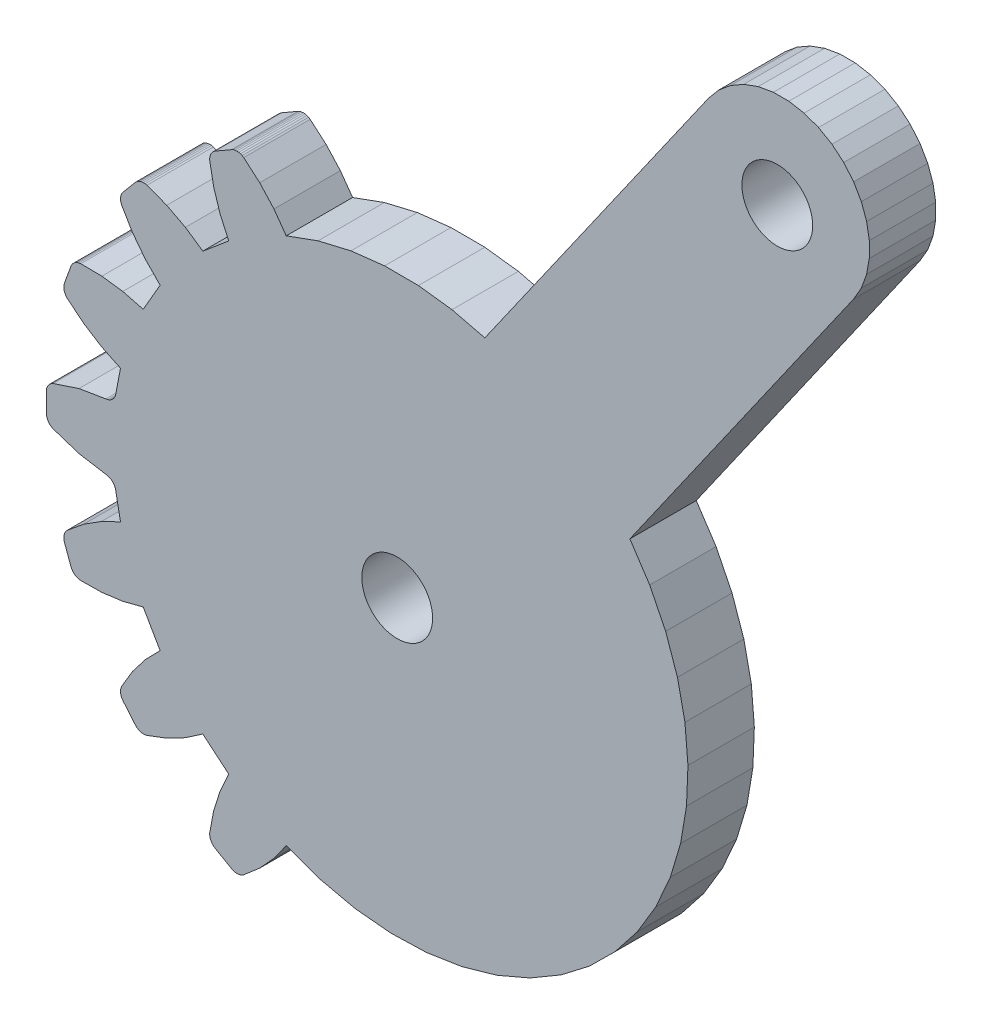
SolidWorks part; units mm, degrees
ref_plane "Front Plane" through (0, 0, 0) normal (0, 0, 1) x (1, 0, 0)
ref_plane "Top Plane" through (0, 0, 0) normal (0, 1, 0) x (1, 0, 0)
ref_plane "Right Plane" through (0, 0, 0) normal (1, 0, 0) x (0, 0, -1)
ref_plane "Plane1" through (0, 0, 3) normal (0, 0, 1) x (1, 0, 0)
sketch "Sketch1" plane through (0, 0, 3) normal (0, 0, 1) x (1, 0, 0)
  line L0 (41.2418, 13.6583) -> (41.2, 14.1358)
  line L1 (41.2, 14.1358) -> (41.2418, 14.6133)
  line L2 (41.2418, 14.6133) -> (41.3658, 15.0764)
  line L3 (41.3658, 15.0764) -> (41.5684, 15.5108)
  line L4 (41.5684, 15.5108) -> (41.8434, 15.9035)
  line L5 (41.8434, 15.9035) -> (42.1823, 16.2424)
  line L6 (42.1823, 16.2424) -> (42.575, 16.5174)
  line L7 (42.575, 16.5174) -> (43.0094, 16.72)
  line L8 (43.0094, 16.72) -> (43.4725, 16.844)
  line L9 (43.4725, 16.844) -> (43.95, 16.8858)
  line L10 (43.95, 16.8858) -> (44.4275, 16.844)
  line L11 (44.4275, 16.844) -> (44.8906, 16.72)
  line L12 (44.8906, 16.72) -> (45.325, 16.5174)
  line L13 (45.325, 16.5174) -> (45.7177, 16.2424)
  line L14 (45.7177, 16.2424) -> (46.0566, 15.9035)
  line L15 (46.0566, 15.9035) -> (46.3316, 15.5108)
  line L16 (46.3316, 15.5108) -> (46.5342, 15.0764)
  line L17 (46.5342, 15.0764) -> (46.6582, 14.6133)
  line L18 (46.6582, 14.6133) -> (46.7, 14.1358)
  line L19 (46.7, 14.1358) -> (46.6582, 13.6583)
  line L20 (46.6582, 13.6583) -> (46.5342, 13.1953)
  line L21 (46.5342, 13.1953) -> (46.3316, 12.7608)
  line L22 (46.3316, 12.7608) -> (46.0566, 12.3681)
  line L23 (46.0566, 12.3681) -> (45.7177, 12.0292)
  line L24 (45.7177, 12.0292) -> (45.325, 11.7542)
  line L25 (45.325, 11.7542) -> (44.8906, 11.5517)
  line L26 (44.8906, 11.5517) -> (44.4275, 11.4276)
  line L27 (44.4275, 11.4276) -> (43.95, 11.3858)
  line L28 (43.95, 11.3858) -> (43.4725, 11.4276)
  line L29 (43.4725, 11.4276) -> (43.0094, 11.5517)
  line L30 (43.0094, 11.5517) -> (42.575, 11.7542)
  line L31 (42.575, 11.7542) -> (42.1823, 12.0292)
  line L32 (42.1823, 12.0292) -> (41.8434, 12.3681)
  line L33 (41.8434, 12.3681) -> (41.5684, 12.7608)
  line L34 (41.5684, 12.7608) -> (41.3658, 13.1953)
  line L35 (41.3658, 13.1953) -> (41.2418, 13.6583)
  line L36 (30.938, 12.5267) -> (30.9937, 12.4646)
  line L37 (30.9937, 12.4646) -> (31.0383, 12.3942)
  line L38 (31.0383, 12.3942) -> (31.0705, 12.3173)
  line L39 (31.0705, 12.3173) -> (31.0896, 12.2361)
  line L40 (31.0896, 12.2361) -> (31.3026, 11.1288)
  line L41 (31.3026, 11.1288) -> (30.4429, 10.7165)
  line L42 (30.4429, 10.7165) -> (29.6383, 10.2049)
  line L43 (29.6383, 10.2049) -> (28.9004, 9.6011)
  line L44 (28.9004, 9.6011) -> (28.8438, 9.5394)
  line L45 (28.8438, 9.5394) -> (28.7983, 9.469)
  line L46 (28.7983, 9.469) -> (28.7652, 9.392)
  line L47 (28.7652, 9.392) -> (28.7454, 9.3106)
  line L48 (28.7454, 9.3106) -> (28.7395, 9.227)
  line L49 (28.7395, 9.227) -> (28.7477, 9.1436)
  line L50 (28.7477, 9.1436) -> (28.7696, 9.0627)
  line L51 (28.7696, 9.0627) -> (29.0602, 8.2643)
  line L52 (29.0602, 8.2643) -> (29.0954, 8.1882)
  line L53 (29.0954, 8.1882) -> (29.1427, 8.1191)
  line L54 (29.1427, 8.1191) -> (29.201, 8.0588)
  line L55 (29.201, 8.0588) -> (29.2685, 8.0092)
  line L56 (29.2685, 8.0092) -> (29.3433, 7.9715)
  line L57 (29.3433, 7.9715) -> (29.4234, 7.9468)
  line L58 (29.4234, 7.9468) -> (29.5065, 7.9358)
  line L59 (29.5065, 7.9358) -> (30.4599, 7.9477)
  line L60 (30.4599, 7.9477) -> (31.405, 8.0729)
  line L61 (31.405, 8.0729) -> (32.3286, 8.3097)
  line L62 (32.3286, 8.3097) -> (33.0938, 6.9844)
  line L63 (33.0938, 6.9844) -> (32.4269, 6.303)
  line L64 (32.4269, 6.303) -> (31.8459, 5.547)
  line L65 (31.8459, 5.547) -> (31.3589, 4.7273)
  line L66 (31.3589, 4.7273) -> (31.3269, 4.6499)
  line L67 (31.3269, 4.6499) -> (31.3082, 4.5682)
  line L68 (31.3082, 4.5682) -> (31.3034, 4.4846)
  line L69 (31.3034, 4.4846) -> (31.3127, 4.4013)
  line L70 (31.3127, 4.4013) -> (31.3357, 4.3207)
  line L71 (31.3357, 4.3207) -> (31.3719, 4.2451)
  line L72 (31.3719, 4.2451) -> (31.4202, 4.1766)
  line L73 (31.4202, 4.1766) -> (31.9664, 3.5258)
  line L74 (31.9664, 3.5258) -> (32.0254, 3.4663)
  line L75 (32.0254, 3.4663) -> (32.0936, 3.4176)
  line L76 (32.0936, 3.4176) -> (32.1689, 3.3809)
  line L77 (32.1689, 3.3809) -> (32.2493, 3.3573)
  line L78 (32.2493, 3.3573) -> (32.3325, 3.3474)
  line L79 (32.3325, 3.3474) -> (32.4162, 3.3517)
  line L80 (32.4162, 3.3517) -> (32.4981, 3.3698)
  line L81 (32.4981, 3.3698) -> (33.3899, 3.707)
  line L82 (33.3899, 3.707) -> (34.2352, 4.1479)
  line L83 (34.2352, 4.1479) -> (35.0221, 4.6863)
  line L84 (35.0221, 4.6863) -> (36.1944, 3.7027)
  line L85 (36.1944, 3.7027) -> (35.8008, 2.8342)
  line L86 (35.8008, 2.8342) -> (35.5134, 1.9252)
  line L87 (35.5134, 1.9252) -> (35.3361, 0.9883)
  line L88 (35.3361, 0.9883) -> (35.3325, 0.9046)
  line L89 (35.3325, 0.9046) -> (35.3429, 0.8215)
  line L90 (35.3429, 0.8215) -> (35.367, 0.7412)
  line L91 (35.367, 0.7412) -> (35.4042, 0.6661)
  line L92 (35.4042, 0.6661) -> (35.4534, 0.5983)
  line L93 (35.4534, 0.5983) -> (35.5133, 0.5396)
  line L94 (35.5133, 0.5396) -> (35.5821, 0.4918)
  line L95 (35.5821, 0.4918) -> (36.3179, 0.067)
  line L96 (36.3179, 0.067) -> (36.3937, 0.0313)
  line L97 (36.3937, 0.0313) -> (36.4745, 0.0088)
  line L98 (36.4745, 0.0088) -> (36.5578, 0.0001)
  line L99 (36.5578, 0.0001) -> (36.6414, 0.0054)
  line L100 (36.6414, 0.0054) -> (36.723, 0.0247)
  line L101 (36.723, 0.0247) -> (36.8002, 0.0572)
  line L102 (36.8002, 0.0572) -> (36.8709, 0.1022)
  line L103 (36.8709, 0.1022) -> (37.5936, 0.7242)
  line L104 (37.5936, 0.7242) -> (38.2371, 1.4276)
  line L105 (38.2371, 1.4276) -> (38.7925, 2.2027)
  line L106 (38.7925, 2.2027) -> (40.321, 1.6526)
  line L107 (40.321, 1.6526) -> (41.9062, 1.2975)
  line L108 (41.9062, 1.2975) -> (43.5233, 1.1428)
  line L109 (43.5233, 1.1428) -> (45.1471, 1.191)
  line L110 (45.1471, 1.191) -> (46.7522, 1.4414)
  line L111 (46.7522, 1.4414) -> (48.3136, 1.89)
  line L112 (48.3136, 1.89) -> (49.8068, 2.5299)
  line L113 (49.8068, 2.5299) -> (51.2085, 3.3509)
  line L114 (51.2085, 3.3509) -> (52.4969, 4.3404)
  line L115 (52.4969, 4.3404) -> (53.6519, 5.4828)
  line L116 (53.6519, 5.4828) -> (54.6553, 6.7604)
  line L117 (54.6553, 6.7604) -> (55.4915, 8.1531)
  line L118 (55.4915, 8.1531) -> (56.1476, 9.6393)
  line L119 (56.1476, 9.6393) -> (56.6132, 11.1956)
  line L120 (56.6132, 11.1956) -> (56.881, 12.7979)
  line L121 (56.881, 12.7979) -> (56.9469, 14.4211)
  line L122 (56.9469, 14.4211) -> (56.8098, 16.0398)
  line L123 (56.8098, 16.0398) -> (56.4719, 17.6288)
  line L124 (56.4719, 17.6288) -> (55.9385, 19.1632)
  line L125 (55.9385, 19.1632) -> (55.2179, 20.6192)
  line L126 (55.2179, 20.6192) -> (54.3214, 21.9739)
  line L127 (54.3214, 21.9739) -> (64.4339, 36.4161)
  line L128 (64.4339, 36.4161) -> (64.7825, 37.0199)
  line L129 (64.7825, 37.0199) -> (65.021, 37.6751)
  line L130 (65.021, 37.6751) -> (65.1421, 38.3617)
  line L131 (65.1421, 38.3617) -> (65.1421, 39.059)
  line L132 (65.1421, 39.059) -> (65.021, 39.7456)
  line L133 (65.021, 39.7456) -> (64.7825, 40.4008)
  line L134 (64.7825, 40.4008) -> (64.4339, 41.0047)
  line L135 (64.4339, 41.0047) -> (63.9857, 41.5388)
  line L136 (63.9857, 41.5388) -> (63.4516, 41.987)
  line L137 (63.4516, 41.987) -> (62.8478, 42.3356)
  line L138 (62.8478, 42.3356) -> (62.1926, 42.5741)
  line L139 (62.1926, 42.5741) -> (61.5059, 42.6951)
  line L140 (61.5059, 42.6951) -> (60.8087, 42.6951)
  line L141 (60.8087, 42.6951) -> (60.122, 42.5741)
  line L142 (60.122, 42.5741) -> (59.4668, 42.3356)
  line L143 (59.4668, 42.3356) -> (58.863, 41.987)
  line L144 (58.863, 41.987) -> (58.3289, 41.5388)
  line L145 (58.3289, 41.5388) -> (57.8807, 41.0047)
  line L146 (57.8807, 41.0047) -> (47.7681, 26.5625)
  line L147 (47.7681, 26.5625) -> (46.2828, 26.9248)
  line L148 (46.2828, 26.9248) -> (44.7652, 27.1102)
  line L149 (44.7652, 27.1102) -> (43.2363, 27.1162)
  line L150 (43.2363, 27.1162) -> (41.7173, 26.9426)
  line L151 (41.7173, 26.9426) -> (40.2291, 26.5919)
  line L152 (40.2291, 26.5919) -> (38.7925, 26.0689)
  line L153 (38.7925, 26.0689) -> (38.2371, 26.844)
  line L154 (38.2371, 26.844) -> (37.5936, 27.5475)
  line L155 (37.5936, 27.5475) -> (36.8709, 28.1694)
  line L156 (36.8709, 28.1694) -> (36.8002, 28.2144)
  line L157 (36.8002, 28.2144) -> (36.723, 28.247)
  line L158 (36.723, 28.247) -> (36.6414, 28.2662)
  line L159 (36.6414, 28.2662) -> (36.5578, 28.2715)
  line L160 (36.5578, 28.2715) -> (36.4745, 28.2628)
  line L161 (36.4745, 28.2628) -> (36.3937, 28.2403)
  line L162 (36.3937, 28.2403) -> (36.3179, 28.2046)
  line L163 (36.3179, 28.2046) -> (35.5821, 27.7798)
  line L164 (35.5821, 27.7798) -> (35.5133, 27.732)
  line L165 (35.5133, 27.732) -> (35.4534, 27.6733)
  line L166 (35.4534, 27.6733) -> (35.4042, 27.6055)
  line L167 (35.4042, 27.6055) -> (35.367, 27.5304)
  line L168 (35.367, 27.5304) -> (35.3429, 27.4501)
  line L169 (35.3429, 27.4501) -> (35.3325, 27.367)
  line L170 (35.3325, 27.367) -> (35.3361, 27.2833)
  line L171 (35.3361, 27.2833) -> (35.5134, 26.3465)
  line L172 (35.5134, 26.3465) -> (35.8008, 25.4374)
  line L173 (35.8008, 25.4374) -> (36.1944, 24.5689)
  line L174 (36.1944, 24.5689) -> (35.0221, 23.5853)
  line L175 (35.0221, 23.5853) -> (34.2352, 24.1237)
  line L176 (34.2352, 24.1237) -> (33.3899, 24.5646)
  line L177 (33.3899, 24.5646) -> (32.4981, 24.9018)
  line L178 (32.4981, 24.9018) -> (32.4162, 24.92)
  line L179 (32.4162, 24.92) -> (32.3325, 24.9242)
  line L180 (32.3325, 24.9242) -> (32.2493, 24.9143)
  line L181 (32.2493, 24.9143) -> (32.1689, 24.8907)
  line L182 (32.1689, 24.8907) -> (32.0936, 24.8541)
  line L183 (32.0936, 24.8541) -> (32.0254, 24.8053)
  line L184 (32.0254, 24.8053) -> (31.9664, 24.7458)
  line L185 (31.9664, 24.7458) -> (31.4202, 24.095)
  line L186 (31.4202, 24.095) -> (31.3719, 24.0265)
  line L187 (31.3719, 24.0265) -> (31.3357, 23.9509)
  line L188 (31.3357, 23.9509) -> (31.3127, 23.8703)
  line L189 (31.3127, 23.8703) -> (31.3034, 23.7871)
  line L190 (31.3034, 23.7871) -> (31.3082, 23.7034)
  line L191 (31.3082, 23.7034) -> (31.3269, 23.6217)
  line L192 (31.3269, 23.6217) -> (31.3589, 23.5443)
  line L193 (31.3589, 23.5443) -> (31.8459, 22.7246)
  line L194 (31.8459, 22.7246) -> (32.4269, 21.9686)
  line L195 (32.4269, 21.9686) -> (33.0938, 21.2872)
  line L196 (33.0938, 21.2872) -> (32.3286, 19.9619)
  line L197 (32.3286, 19.9619) -> (31.405, 20.1987)
  line L198 (31.405, 20.1987) -> (30.4599, 20.3239)
  line L199 (30.4599, 20.3239) -> (29.5065, 20.3358)
  line L200 (29.5065, 20.3358) -> (29.4234, 20.3248)
  line L201 (29.4234, 20.3248) -> (29.3433, 20.3001)
  line L202 (29.3433, 20.3001) -> (29.2685, 20.2624)
  line L203 (29.2685, 20.2624) -> (29.201, 20.2128)
  line L204 (29.201, 20.2128) -> (29.1427, 20.1525)
  line L205 (29.1427, 20.1525) -> (29.0954, 20.0834)
  line L206 (29.0954, 20.0834) -> (29.0602, 20.0073)
  line L207 (29.0602, 20.0073) -> (28.7696, 19.2089)
  line L208 (28.7696, 19.2089) -> (28.7477, 19.1281)
  line L209 (28.7477, 19.1281) -> (28.7395, 19.0447)
  line L210 (28.7395, 19.0447) -> (28.7454, 18.9611)
  line L211 (28.7454, 18.9611) -> (28.7652, 18.8796)
  line L212 (28.7652, 18.8796) -> (28.7983, 18.8026)
  line L213 (28.7983, 18.8026) -> (28.8438, 18.7323)
  line L214 (28.8438, 18.7323) -> (28.9004, 18.6705)
  line L215 (28.9004, 18.6705) -> (29.6383, 18.0668)
  line L216 (29.6383, 18.0668) -> (30.4429, 17.5551)
  line L217 (30.4429, 17.5551) -> (31.3026, 17.1428)
  line L218 (31.3026, 17.1428) -> (31.0896, 16.0355)
  line L219 (31.0896, 16.0355) -> (31.0705, 15.9543)
  line L220 (31.0705, 15.9543) -> (31.0383, 15.8774)
  line L221 (31.0383, 15.8774) -> (30.9937, 15.807)
  line L222 (30.9937, 15.807) -> (30.938, 15.7449)
  line L223 (30.938, 15.7449) -> (30.8728, 15.6929)
  line L224 (30.8728, 15.6929) -> (30.7998, 15.6525)
  line L225 (30.7998, 15.6525) -> (30.7212, 15.6248)
  line L226 (30.7212, 15.6248) -> (30.639, 15.6106)
  line L227 (30.639, 15.6106) -> (29.4253, 15.4081)
  line L228 (29.4253, 15.4081) -> (28.257, 15.0219)
  line L229 (28.257, 15.0219) -> (28.1827, 14.9832)
  line L230 (28.1827, 14.9832) -> (28.1159, 14.9326)
  line L231 (28.1159, 14.9326) -> (28.0585, 14.8716)
  line L232 (28.0585, 14.8716) -> (28.012, 14.8018)
  line L233 (28.012, 14.8018) -> (27.9779, 14.7253)
  line L234 (27.9779, 14.7253) -> (27.957, 14.6441)
  line L235 (27.957, 14.6441) -> (27.95, 14.5606)
  line L236 (27.95, 14.5606) -> (27.95, 13.711)
  line L237 (27.95, 13.711) -> (27.957, 13.6275)
  line L238 (27.957, 13.6275) -> (27.9779, 13.5463)
  line L239 (27.9779, 13.5463) -> (28.012, 13.4698)
  line L240 (28.012, 13.4698) -> (28.0585, 13.4)
  line L241 (28.0585, 13.4) -> (28.1159, 13.339)
  line L242 (28.1159, 13.339) -> (28.1827, 13.2884)
  line L243 (28.1827, 13.2884) -> (28.257, 13.2497)
  line L244 (28.257, 13.2497) -> (29.4253, 12.8635)
  line L245 (29.4253, 12.8635) -> (30.639, 12.6611)
  line L246 (30.639, 12.6611) -> (30.7212, 12.6468)
  line L247 (30.7212, 12.6468) -> (30.7998, 12.6191)
  line L248 (30.7998, 12.6191) -> (30.8728, 12.5787)
  line L249 (30.8728, 12.5787) -> (30.938, 12.5267)
  line L250 (60.7883, 36.6177) -> (60.4305, 36.7135)
  line L251 (60.4305, 36.7135) -> (60.0948, 36.8701)
  line L252 (60.0948, 36.8701) -> (59.7914, 37.0825)
  line L253 (59.7914, 37.0825) -> (59.5294, 37.3444)
  line L254 (59.5294, 37.3444) -> (59.317, 37.6479)
  line L255 (59.317, 37.6479) -> (59.1604, 37.9836)
  line L256 (59.1604, 37.9836) -> (59.0646, 38.3414)
  line L257 (59.0646, 38.3414) -> (59.0323, 38.7104)
  line L258 (59.0323, 38.7104) -> (59.0646, 39.0794)
  line L259 (59.0646, 39.0794) -> (59.1604, 39.4372)
  line L260 (59.1604, 39.4372) -> (59.317, 39.7729)
  line L261 (59.317, 39.7729) -> (59.5294, 40.0763)
  line L262 (59.5294, 40.0763) -> (59.7914, 40.3382)
  line L263 (59.7914, 40.3382) -> (60.0948, 40.5507)
  line L264 (60.0948, 40.5507) -> (60.4305, 40.7072)
  line L265 (60.4305, 40.7072) -> (60.7883, 40.8031)
  line L266 (60.7883, 40.8031) -> (61.1573, 40.8354)
  line L267 (61.1573, 40.8354) -> (61.5263, 40.8031)
  line L268 (61.5263, 40.8031) -> (61.8841, 40.7072)
  line L269 (61.8841, 40.7072) -> (62.2198, 40.5507)
  line L270 (62.2198, 40.5507) -> (62.5232, 40.3382)
  line L271 (62.5232, 40.3382) -> (62.7851, 40.0763)
  line L272 (62.7851, 40.0763) -> (62.9976, 39.7729)
  line L273 (62.9976, 39.7729) -> (63.1541, 39.4372)
  line L274 (63.1541, 39.4372) -> (63.25, 39.0794)
  line L275 (63.25, 39.0794) -> (63.2823, 38.7104)
  line L276 (63.2823, 38.7104) -> (63.25, 38.3414)
  line L277 (63.25, 38.3414) -> (63.1541, 37.9836)
  line L278 (63.1541, 37.9836) -> (62.9976, 37.6479)
  line L279 (62.9976, 37.6479) -> (62.7851, 37.3444)
  line L280 (62.7851, 37.3444) -> (62.5232, 37.0825)
  line L281 (62.5232, 37.0825) -> (62.2198, 36.8701)
  line L282 (62.2198, 36.8701) -> (61.8841, 36.7135)
  line L283 (61.8841, 36.7135) -> (61.5263, 36.6177)
  line L284 (61.5263, 36.6177) -> (61.1573, 36.5854)
  line L285 (61.1573, 36.5854) -> (60.7883, 36.6177)
extrude "Boss-Extrude1" add sketch "Sketch1" against normal blind 3
sketch "Sketch2" plane through (0, 0, 3) normal (0, 0, 1) x (1, 0, 0)
  line L0 (46.7, 14.1358) -> (41.2, 14.1358) construction
  circle A0 centre (43.95, 14.1358) radius 2.75
extrude "Boss-Extrude2" add sketch "Sketch2" against normal blind 3
hole_wizard "M3 Clearance Hole1" positions "Sketch5" profile "Sketch4" hole size "M3" standard "ANSI Metric" end condition up to next
sketch "Sketch5" plane through (0, 0, 3) normal (0, 0, 1) x (1, 0, 0)
  point P0 (43.8071, 14.4101)
sketch "Sketch4" plane through (43.8071, 14.4101, 3) normal (1, 0, 0) x (0, -1, 0)
  line L0 (0, 0) -> (0, 3)
  line L1 (0, 3) -> (1.6, 3)
  line L2 (1.6, 3) -> (1.6, 0)
  line L5 (1.6, 0) -> (0, 0)
  line L11 (0, -6.35) -> (0, 107.95) construction
  dimension "Thru Hole Dia." = 3.2
  dimension "Thru Hole Depth" = 3
sketch "Sketch6" plane through (0, 0, 3) normal (0, 0, 1) x (1, 0, 0)
  line L0 (59.4232, 37.4962) -> (62.7851, 40.0763) construction
  line L1 (59.317, 37.6479) -> (59.5294, 37.3444) construction
  circle A0 centre (61.1042, 38.7862) radius 2.2923
extrude "Boss-Extrude3" add sketch "Sketch6" against normal blind 3
hole_wizard "M3 Clearance Hole2" positions "Sketch7" profile "Sketch8" hole size "M3" standard "ANSI Metric" end condition through all
sketch "Sketch7" plane through (0, 0, 3) normal (0, 0, 1) x (1, 0, 0)
  point P0 (60.9841, 38.3621)
sketch "Sketch8" plane through (60.9841, 38.3621, 3) normal (1, 0, 0) x (0, -1, 0)
  line L0 (0, 0) -> (0, 3)
  line L1 (0, 3) -> (1.6, 3)
  line L2 (1.6, 3) -> (1.6, 0)
  line L5 (1.6, 0) -> (0, 0)
  line L11 (0, -6.35) -> (0, 107.95) construction
  dimension "Thru Hole Dia." = 3.2
  dimension "Thru Hole Depth" = 3
